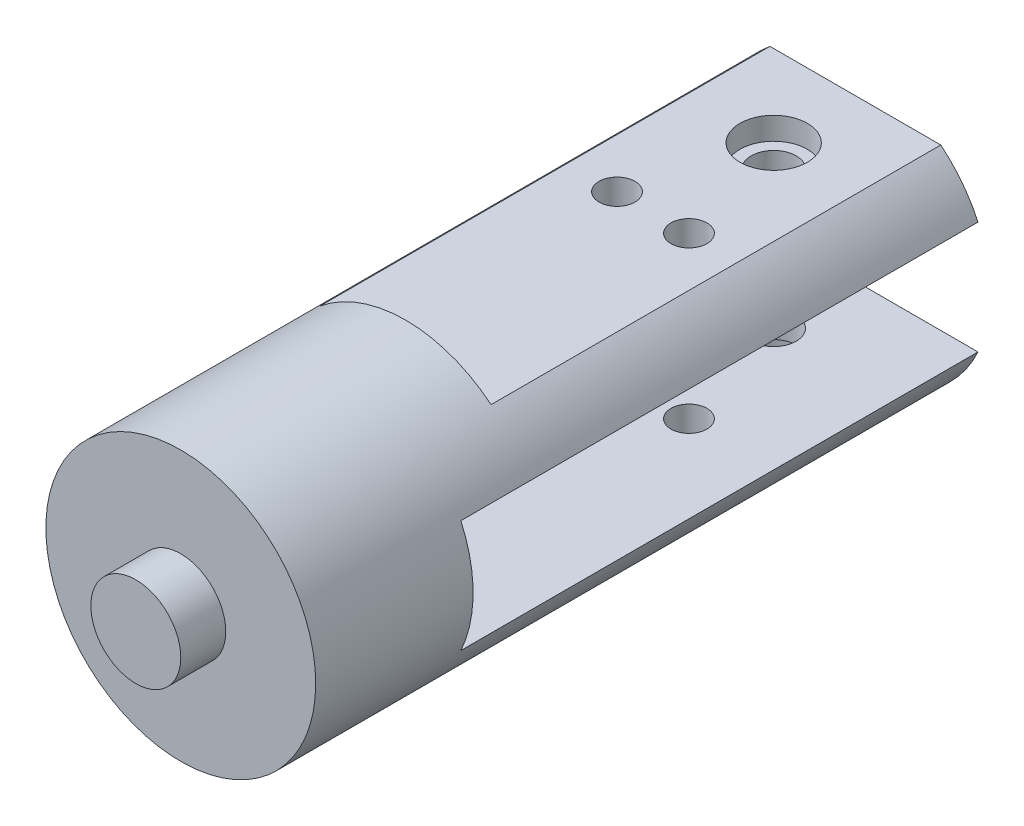
SolidWorks part; units mm, degrees
ref_plane "Ön Düzlem" through (0, 0, 0) normal (0, 0, 1) x (1, 0, 0)
ref_plane "Üst Düzlem" through (0, 0, 0) normal (0, 1, 0) x (1, 0, 0)
ref_plane "Sağ Düzlem" through (0, 0, 0) normal (1, 0, 0) x (0, 0, -1)
sketch "Çizim1" plane through (0, 0, 0) normal (0, 0, 1) x (1, 0, 0)
  circle A0 centre (0, 0) radius 30
  circle A1 centre (0, 0) radius 10
  dimension "D1" = 60
  dimension "D2" = 20
extrude "Yükseklik-Ekstrüzyon2" add sketch "Çizim1" along normal blind 25 contours A0 A1 | A1 region at (-29.1515, 0, 0) region at (0, 0, 0)
extrude "Yükseklik-Ekstrüzyon3" add sketch "Çizim1<4>" along normal blind 35 contours A1 region at (0, 0, 0)
sketch "Çizim1<4>" plane through (0, 0, 0) normal (0, 0, 1) x (1, 0, 0) same geometry as "Çizim1"
extrude "Yükseklik-Ekstrüzyon4" add sketch "Çizim1<5>" against normal blind 125 contours A0 A1 | A1 region at (-29.1515, 0, 0) region at (0, 0, 0)
sketch "Çizim1<5>" plane through (0, 0, 0) normal (0, 0, 1) x (1, 0, 0) same geometry as "Çizim1"
sketch "Çizim3" plane through (0, 0, -125) normal (0, 0, -1) x (-1, 0, 0)
  line L0 (-27.2718, 12.5) -> (-27.2718, -12.5)
  line L1 (-27.2718, 12.5) -> (27.2718, 12.5)
  line L2 (-27.2718, 12.5) -> (-27.2718, -12.5)
  line L3 (-27.2718, -12.5) -> (27.2718, -12.5)
  line L4 (27.2718, 12.5) -> (27.2718, -12.5)
  line L5 (-27.2718, 12.5) -> (27.2718, -12.5) construction
  line L6 (-27.2718, -12.5) -> (27.2718, 12.5) construction
  line L7 (27.2718, 12.5) -> (27.2718, -12.5)
  circle A0 centre (0, 0) radius 30 construction
  arc A1 (-27.2718, 12.5) -> (-27.2718, -12.5) centre (0, 0) ccw
  arc A2 (27.2718, 12.5) -> (27.2718, -12.5) centre (0, 0) cw
  point P0 (0, 0)
  circle M5 centre (0, 0) radius 30
  dimension "D1" = 25
extrude "Kes-Ekstrüzyon1" cut sketch "Çizim3" against normal blind 115 contours L0 M5 | L4 M5 | L2 L1 L4 L3 region at (28.3674, 0, -125) region at (-28.3674, 0, -125)
sketch "Çizim4" plane through (0, 0, -125) normal (0, 0, -1) x (-1, 0, 0)
  line L0 (-19, 23.2164) -> (19, 23.2164)
  line L1 (0, 23.2164) -> (0, 0) construction
  line L2 (-30, 0) -> (30, 0) construction
  line L3 (-19, -23.2164) -> (19, -23.2164)
  arc A0 (27.2718, 12.5) -> (-27.2718, 12.5) centre (0, 0) ccw construction
  arc A1 (-27.2718, 12.5) -> (-27.2718, -12.5) centre (0, 0) ccw construction
  arc A2 (27.2718, -12.5) -> (27.2718, 12.5) centre (0, 0) ccw construction
  arc A3 (-19, 23.2164) -> (19, 23.2164) centre (0, 0) cw
  arc A4 (-19, -23.2164) -> (19, -23.2164) centre (0, 0) ccw
  dimension "D1" = 38
extrude "Kes-Ekstrüzyon2" cut sketch "Çizim4" against normal blind 100
sketch "Çizim5" plane through (0, 23.2164, 0) normal (0, 1, 0) x (1, 0, 0)
  line L0 (-19, 25) -> (-19, 125) construction
  line L1 (19, 25) -> (19, 125) construction
  line L2 (19, 125) -> (-19, 125) construction
  circle A0 centre (-8, 80) radius 4
  circle A1 centre (8, 80) radius 4
  dimension "D1" = 8
  dimension "D2" = 11
  dimension "D3" = 11
  dimension "D4" = 45
extrude "Kes-Ekstrüzyon3" cut sketch "Çizim5" against normal blind 100
sketch "Çizim6" plane through (0, 23.2164, 0) normal (0, 1, 0) x (1, 0, 0)
  line L0 (0, 125) -> (0, 71.1384) construction
  line L1 (19, 125) -> (-19, 125) construction
  circle A0 centre (0, 106.843) radius 7.5
  circle A1 centre (0, 106.843) radius 5
  dimension "D1" = 15
  dimension "D2" = 10
extrude "Kes-Ekstrüzyon4" cut sketch "Çizim6" against normal blind 5 contours L0 A1 | A1 L0 | L0 A0 A1 | A0 L0 A1 region at (5.1847, 23.2164, -112.0277) region at (-0.1677, 23.2164, -113.093) region at (2.1221, 23.2164, -106.843) region at (-2.1221, 23.2164, -106.843)
extrude "Kes-Ekstrüzyon5" cut sketch "Çizim6<3>" against normal up to surface (10.7164 mm away) contours L0 A1 | A1 L0 region at (2.1221, 23.2164, -106.843) region at (-2.1221, 23.2164, -106.843) up to face at (-8, 12.5, -84)
sketch "Çizim6<3>" plane through (0, 23.2164, 0) normal (0, 1, 0) x (1, 0, 0) same geometry as "Çizim6"
mirror "Aynalama1" about plane through (0, 0, 0) normal (0, 1, 0) of "Kes-Ekstrüzyon5", "Kes-Ekstrüzyon4"
scale "Ölçek1" scale about centroid uniform scaling yes scale factor 0.3
